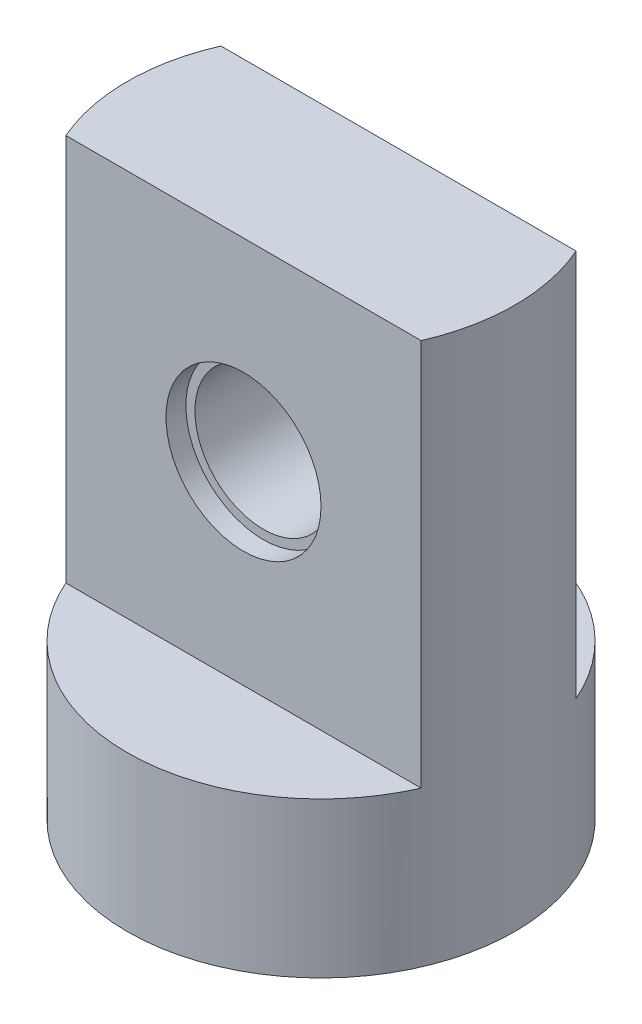
SolidWorks part; units mm, degrees
ref_plane "Front Plane" through (0, 0, 0) normal (0, 0, 1) x (1, 0, 0)
ref_plane "Top Plane" through (0, 0, 0) normal (0, 1, 0) x (1, 0, 0)
ref_plane "Right Plane" through (0, 0, 0) normal (1, 0, 0) x (0, 0, -1)
sketch "Sketch1" plane through (0, 0, 0) normal (0, 1, 0) x (1, 0, 0)
  line L2 (6.8739, 3) -> (-6.8739, 3)
  line L5 (-6.8739, -3) -> (6.8739, -3)
  circle A0 centre (0, 0) radius 7.5
  dimension "D1" = 15
extrude "Boss-Extrude6" add sketch "Sketch1" along normal blind 6 contours L5 A0 L2 | A0 region at (0, 0, 0)
extrude "Boss-Extrude7" add sketch "Sketch1<9>" along normal blind 21 contours L5 A0 L2 region at (0, 0, 0)
sketch "Sketch1<9>" plane through (0, 0, 0) normal (0, 1, 0) x (1, 0, 0) same geometry as "Sketch1"
sketch "Sketch4" plane through (0, 0, 3) normal (0, 0, 1) x (1, 0, 0)
  line L1 (6.8739, 6) -> (6.8739, 21)
  circle A0 centre (0, 13.5) radius 2.9
  circle A1 centre (0, 13.5) radius 2.65
  dimension "D1" = 5.3
  dimension "D2" = 5.8
extrude "Cut-Extrude7" cut sketch "Sketch4" against normal blind 6 contours A1
sketch "Sketch7" plane through (0, 0, 3) normal (0, 0, 1) x (1, 0, 0)
  circle A0 centre (0, 13.5) radius 3
  point P0 (0, 13.5)
extrude "Cut-Extrude8" cut sketch "Sketch7" against normal blind 0.77
sketch "Sketch8" plane through (0, 0, 0) normal (0, -1, 0) x (1, 0, 0)
  circle A0 centre (0, 0) radius 2.3
extrude "Cut-Extrude9" cut sketch "Sketch8" against normal blind 6
